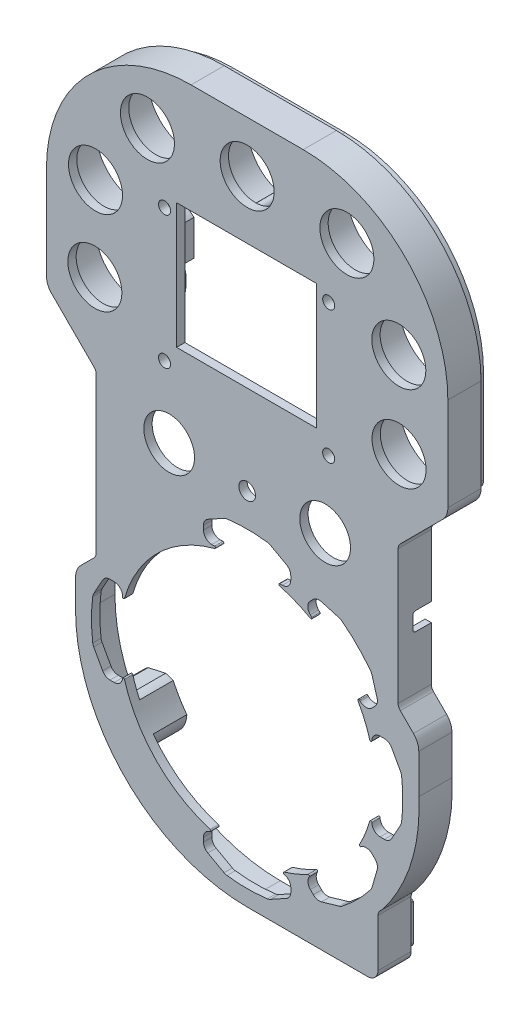
SolidWorks part; units mm, degrees
ref_plane "Front Plane" through (0, 0, 0) normal (0, 0, 1) x (1, 0, 0)
ref_plane "Top Plane" through (0, 0, 0) normal (0, 1, 0) x (1, 0, 0)
ref_plane "Right Plane" through (0, 0, 0) normal (1, 0, 0) x (0, 0, -1)
sketch "Sketch1" plane through (0, 0, 0) normal (0, 0, 1) x (1, 0, 0)
  line L36 (8.4982, -30) -> (7.3207, -30)
  line L37 (-7.3216, -30) -> (-8.502, -30)
  line L38 (-10.502, -32) -> (-10.502, -33.0199)
  line L39 (-9.469, -34.7705) -> (-5.5638, -36.9277)
  line L40 (5.5641, -36.9255) -> (9.4653, -34.7705)
  line L41 (10.4982, -33.0199) -> (10.4982, -32)
  line L42 (27.2278, -15.1986) -> (26.1368, -16.2896)
  line L43 (16.1034, -26.323) -> (15.2069, -27.2195)
  line L44 (15.2069, -30.0479) -> (15.928, -30.7691)
  line L45 (17.8964, -31.2766) -> (22.1831, -30.0405)
  line L46 (30.0502, -22.1703) -> (31.2849, -17.888)
  line L47 (30.7774, -15.9197) -> (30.0563, -15.1986)
  line L48 (29.9995, 8.3209) -> (29.9995, 6.3328)
  line L49 (29.9995, -6.7043) -> (29.9995, -8.6793)
  line L50 (31.9995, -10.6793) -> (33.0194, -10.6793)
  line L51 (34.77, -9.6463) -> (36.9272, -5.7411)
  line L52 (36.925, 5.3868) -> (34.77, 9.2879)
  line L53 (33.0194, 10.3209) -> (31.9995, 10.3209)
  line L54 (15.1817, 27.2112) -> (17.0463, 25.3466)
  line L55 (25.5318, 16.8611) -> (27.2026, 15.1902)
  line L56 (30.0311, 15.1902) -> (30.7522, 15.9114)
  line L57 (31.2597, 17.8797) -> (30.0237, 22.1664)
  line L58 (22.1535, 30.0335) -> (17.8712, 31.2683)
  line L59 (15.9029, 30.7608) -> (15.1817, 30.0396)
  line L60 (-8.5066, 30) -> (-5.5963, 30)
  line L61 (5.5954, 30) -> (8.4935, 30)
  line L62 (10.4935, 32) -> (10.4935, 33.0198)
  line L63 (9.4606, 34.7705) -> (5.5554, 36.9277)
  line L64 (-5.5725, 36.9254) -> (-9.4737, 34.7705)
  line L65 (-10.5066, 33.0198) -> (-10.5066, 32)
  line L66 (-30, -8.5009) -> (-30, -6.7063)
  line L67 (-30, 6.3349) -> (-30, 8.4993)
  line L68 (-32, 10.4993) -> (-33.0198, 10.4993)
  line L69 (-34.7705, 9.4663) -> (-36.9277, 5.5612)
  line L70 (-36.9254, -5.5668) -> (-34.7705, -9.4679)
  line L71 (-33.0198, -10.5009) -> (-32, -10.5009)
  line L101 (-41.299, 6.7982) -> (-41.3, -0.001)
  line L102 (-36.8542, 13.0512) -> (-40.0199, 9.8856)
  line L103 (-36.337, 51.567) -> (-36.337, 14.3015)
  line L104 (-47.0212, 62.9828) -> (-36.8553, 52.8168)
  line L105 (-48.3, 88.5) -> (-48.3, 66.0705)
  line L106 (13.5, 123.3) -> (-13.5, 123.3)
  line L107 (48.309, 66.0795) -> (48.3, 88.5)
  line L108 (36.865, 52.8266) -> (47.0307, 62.9922)
  line L109 (36.337, 19.3) -> (36.337, 51.5682)
  line L110 (40.0202, 14.8852) -> (36.8553, 18.0502)
  line L111 (41.299, 2.3183) -> (41.299, 11.7975)
  line L112 (32.0172, -26.0612) -> (32.5244, -25.5541)
  line L113 (31.5, -38.795) -> (31.5, -27.3095)
  line L114 (0, -41.301) -> (28.9995, -41.301)
  circle A1 centre (-18.768, 46) radius 6.1
  circle A4 centre (18.768, 46) radius 6.1
  arc A45 (17.0463, 25.3466) -> (5.5954, 30) centre (-0.0005, -0.1857) ccw
  arc A77 (-8.502, -30) -> (-10.502, -32) centre (-8.502, -32) ccw
  arc A78 (-10.502, -33.0199) -> (-9.469, -34.7705) centre (-8.502, -33.0199) ccw
  arc A79 (-5.5638, -36.9277) -> (-4.8555, -37.1602) centre (-4.5968, -35.177) ccw
  arc A80 (-4.8555, -37.1602) -> (4.8567, -37.1579) centre (-0.0084, 0) ccw
  arc A81 (4.8567, -37.1579) -> (5.5641, -36.9255) centre (4.5971, -35.1748) ccw
  arc A82 (9.4653, -34.7705) -> (10.4982, -33.0199) centre (8.4982, -33.0199) ccw
  arc A83 (10.4982, -32) -> (8.4982, -30) centre (8.4982, -32) ccw
  arc A88 (15.2069, -27.2195) -> (15.2069, -30.0479) centre (16.6211, -28.6337) ccw
  arc A89 (15.928, -30.7691) -> (17.8964, -31.2766) centre (17.3423, -29.3549) ccw
  arc A90 (22.1831, -30.0405) -> (22.8484, -29.7041) centre (21.629, -28.1188) ccw
  arc A91 (22.8484, -29.7041) -> (29.7143, -22.8348) centre (-0.0004, -0.0005) ccw
  arc A92 (29.7143, -22.8348) -> (30.0502, -22.1703) centre (28.1285, -21.6162) ccw
  arc A93 (31.2849, -17.888) -> (30.7774, -15.9197) centre (29.3632, -17.3339) ccw
  arc A94 (30.0563, -15.1986) -> (27.2278, -15.1986) centre (28.642, -16.6128) ccw
  arc A99 (29.9995, -8.6793) -> (31.9995, -10.6793) centre (31.9995, -8.6793) ccw
  arc A100 (33.0194, -10.6793) -> (34.77, -9.6463) centre (33.0194, -8.6793) ccw
  arc A101 (36.9272, -5.7411) -> (37.1598, -5.0328) centre (35.1766, -4.7741) ccw
  arc A102 (37.1598, -5.0328) -> (37.1574, 4.6794) centre (-0.0005, -0.1857) ccw
  arc A103 (37.1574, 4.6794) -> (36.925, 5.3868) centre (35.1743, 4.4198) ccw
  arc A104 (34.77, 9.2879) -> (33.0194, 10.3209) centre (33.0194, 8.3209) ccw
  arc A105 (31.9995, 10.3209) -> (29.9995, 8.3209) centre (31.9995, 8.3209) ccw
  arc A110 (27.2026, 15.1902) -> (30.0311, 15.1902) centre (28.6169, 16.6045) ccw
  arc A111 (30.7522, 15.9114) -> (31.2597, 17.8797) centre (29.338, 17.3256) ccw
  arc A112 (30.0237, 22.1664) -> (29.6872, 22.8318) centre (28.102, 21.6123) ccw
  arc A113 (29.6872, 22.8318) -> (22.818, 29.6976) centre (-0.0164, -0.0171) ccw
  arc A114 (22.818, 29.6976) -> (22.1535, 30.0335) centre (21.5994, 28.1118) ccw
  arc A115 (17.8712, 31.2683) -> (15.9029, 30.7608) centre (17.3171, 29.3465) ccw
  arc A116 (15.1817, 30.0396) -> (15.1817, 27.2112) centre (16.5959, 28.6254) ccw
  arc A121 (8.4935, 30) -> (10.4935, 32) centre (8.4935, 32) ccw
  arc A122 (10.4935, 33.0198) -> (9.4606, 34.7705) centre (8.4935, 33.0198) ccw
  arc A123 (5.5554, 36.9277) -> (4.8471, 37.1602) centre (4.5884, 35.177) ccw
  arc A124 (4.8471, 37.1602) -> (-4.8651, 37.1579) centre (0, 0) ccw
  arc A125 (-4.8651, 37.1579) -> (-5.5725, 36.9254) centre (-4.6055, 35.1748) ccw
  arc A126 (-9.4737, 34.7705) -> (-10.5066, 33.0198) centre (-8.5066, 33.0198) ccw
  arc A127 (-10.5066, 32) -> (-8.5066, 30) centre (-8.5066, 32) ccw
  arc A132 (-30, 8.4993) -> (-32, 10.4993) centre (-32, 8.4993) ccw
  arc A133 (-33.0198, 10.4993) -> (-34.7705, 9.4663) centre (-33.0198, 8.4993) ccw
  arc A134 (-36.9277, 5.5612) -> (-37.1602, 4.8528) centre (-35.177, 4.5941) ccw
  arc A135 (-37.1602, 4.8528) -> (-37.1579, -4.8594) centre (0, 0.0057) ccw
  arc A136 (-37.1579, -4.8594) -> (-36.9254, -5.5668) centre (-35.1748, -4.5997) ccw
  arc A137 (-34.7705, -9.4679) -> (-33.0198, -10.5009) centre (-33.0198, -8.5009) ccw
  arc A138 (-32, -10.5009) -> (-30, -8.5009) centre (-32, -8.5009) ccw
  circle A139 centre (36.55, 71.3501) radius 6.5
  circle A140 centre (36.5, 92.0001) radius 6.5
  circle A141 centre (23.9999, 109.0001) radius 6.5
  circle A142 centre (0.0001, 111) radius 6.5
  circle A143 centre (-24.0001, 108.9999) radius 6.5
  circle A144 centre (-36.5, 91.9999) radius 6.5
  circle A145 centre (-36.65, 71.6499) radius 6.5
  arc A146 (29.9995, 6.3328) -> (25.5318, 16.8611) centre (-0.0005, -0.1857) ccw
  arc A147 (26.1368, -16.2896) -> (29.9995, -6.7043) centre (-0.0005, -0.1857) ccw
  arc A148 (7.3207, -30) -> (16.1034, -26.323) centre (-0.0005, -0.1857) ccw
  arc A149 (-30, -6.7063) -> (-7.3216, -30) centre (-0.0005, -0.1857) ccw
  arc A157 (-41.3, -0.001) -> (0, -41.301) centre (0.0009, -0.0001) ccw
  arc A158 (-40.0199, 9.8856) -> (-41.299, 6.7982) centre (-36.9358, 6.7992) ccw
  arc A159 (-36.8542, 13.0512) -> (-36.337, 14.3015) centre (-38.1114, 14.3035) ccw
  arc A160 (-5.5963, 30) -> (-30, 6.3349) centre (-0.0005, -0.1857) ccw
  arc A161 (-36.337, 51.567) -> (-36.8553, 52.8168) centre (-38.1114, 51.5635) ccw
  arc A162 (-48.3, 66.0705) -> (-47.0212, 62.9828) centre (-43.9368, 66.0688) ccw
  arc A163 (-13.5, 123.3) -> (-48.3, 88.5) centre (-13.4997, 88.4997) ccw
  arc A164 (48.3, 88.5) -> (13.5, 123.3) centre (13.4997, 88.4997) ccw
  arc A165 (47.0307, 62.9922) -> (48.309, 66.0795) centre (43.9392, 66.0805) ccw
  arc A166 (36.865, 52.8266) -> (36.337, 51.5682) centre (38.1601, 51.5431) ccw
  arc A167 (36.337, 19.3) -> (36.8553, 18.0502) centre (38.1114, 19.3035) ccw
  arc A168 (41.299, 11.7975) -> (40.0202, 14.8852) centre (36.9358, 11.7992) ccw
  arc A169 (32.5244, -25.5541) -> (41.299, 2.3183) centre (0.058, -0.0158) ccw
  arc A170 (32.0172, -26.0612) -> (31.5, -27.3095) centre (33.2632, -27.3088) ccw
  arc A171 (28.9995, -41.301) -> (31.5, -38.795) centre (28.9913, -38.7924) ccw
extrude "Boss-Extrude1" add sketch "Sketch1" along normal blind 2
sketch "Sketch2" plane through (0, 0, 2) normal (0, 0, 1) x (1, 0, 0)
  line L21 (16.773, 59.804) -> (19.873, 59.804)
  line L22 (22.373, 62.304) -> (22.373, 94.804)
  line L23 (19.873, 97.304) -> (16.773, 97.304)
  line L24 (16.773, 97.304) -> (-17.027, 97.304)
  line L28 (-17.027, 59.804) -> (16.773, 59.804)
  line L32 (-22.627, 94.804) -> (-22.627, 62.304)
  line L33 (-20.127, 59.804) -> (-17.027, 59.804)
  line L35 (-17.027, 97.304) -> (-20.127, 97.304)
  line L37 (-17.027, 97.304) -> (16.773, 97.304)
  spline S6 degree 3 poles (19.873, 59.804) (21.3375, 59.804) (22.373, 60.8395) (22.373, 62.304) knots 0 0 0 0 1 1 1 1 weights 1 0.804738 0.804738 1
  spline S7 degree 3 poles (22.373, 94.804) (22.373, 96.2685) (21.3375, 97.304) (19.873, 97.304) knots 0 0 0 0 1 1 1 1 weights 1 0.804738 0.804738 1
  spline S8 degree 3 poles (-20.127, 97.304) (-21.5915, 97.304) (-22.627, 96.2685) (-22.627, 94.804) knots 0 0 0 0 1 1 1 1 weights 1 0.804738 0.804738 1
  spline S9 degree 3 poles (-22.627, 62.304) (-22.627, 60.8395) (-21.5915, 59.804) (-20.127, 59.804) knots 0 0 0 0 1 1 1 1 weights 1 0.804738 0.804738 1
sketch "Sketch3" plane through (0, 0, 2) normal (0, 0, 1) x (1, 0, 0)
  line L64 (-17.027, 99.304) -> (-20.127, 99.304)
  line L65 (-24.627, 94.804) -> (-24.627, 62.304)
  line L66 (-20.127, 57.804) -> (-17.027, 57.804)
  line L67 (-17.027, 57.804) -> (16.773, 57.804)
  line L68 (16.773, 57.804) -> (19.873, 57.804)
  line L69 (24.373, 62.304) -> (24.373, 94.804)
  line L70 (19.873, 99.304) -> (16.773, 99.304)
  line L71 (16.773, 99.304) -> (-17.027, 99.304)
  line L72 (-17.027, 99.304) -> (-20.127, 99.304)
  line L73 (-24.627, 94.804) -> (-24.627, 62.304)
  line L74 (-20.127, 57.804) -> (-17.027, 57.804)
  line L75 (-17.027, 57.804) -> (16.773, 57.804)
  line L76 (16.773, 57.804) -> (19.873, 57.804)
  line L77 (24.373, 62.304) -> (24.373, 94.804)
  line L78 (19.873, 99.304) -> (16.773, 99.304)
  line L79 (16.773, 99.304) -> (-17.027, 99.304)
  arc A29 (-20.127, 99.304) -> (-24.627, 94.804) centre (-20.127, 94.804) ccw
  arc A30 (-24.627, 62.304) -> (-20.127, 57.804) centre (-20.127, 62.304) ccw
  arc A31 (19.873, 57.804) -> (24.373, 62.304) centre (19.873, 62.304) ccw
  arc A32 (24.373, 94.804) -> (19.873, 99.304) centre (19.873, 94.804) ccw
  arc A33 (-20.127, 99.304) -> (-24.627, 94.804) centre (-20.127, 94.804) ccw
  arc A34 (-24.627, 62.304) -> (-20.127, 57.804) centre (-20.127, 62.304) ccw
  arc A35 (19.873, 57.804) -> (24.373, 62.304) centre (19.873, 62.304) ccw
  arc A36 (24.373, 94.804) -> (19.873, 99.304) centre (19.873, 94.804) ccw
  dimension "D1" = 2
sketch "Sketch4" plane through (0, 0, 2) normal (0, 0, 1) x (1, 0, 0)
  line L4 (-16.977, 66.854) -> (16.723, 66.854)
  line L5 (16.723, 66.854) -> (16.723, 97.004)
  line L6 (-16.977, 97.004) -> (-16.977, 66.854)
  line L7 (-16.977, 97.004) -> (16.723, 97.004)
extrude "Cut-Extrude1" cut sketch "Sketch4" against normal through all
sketch "Sketch5" plane through (0, 0, 0) normal (0, 0, 1) x (1, 0, 0)
  line L58 (-22.877, 94.804) -> (-22.877, 62.304)
  line L59 (-20.127, 59.554) -> (-17.027, 59.554)
  line L60 (-17.027, 59.554) -> (16.773, 59.554)
  line L61 (16.773, 59.554) -> (19.873, 59.554)
  line L62 (22.623, 62.304) -> (22.623, 94.804)
  line L63 (19.873, 97.554) -> (16.773, 97.554)
  line L64 (16.773, 97.554) -> (-17.027, 97.554)
  line L65 (-17.027, 97.554) -> (-20.127, 97.554)
  line L66 (-22.877, 94.804) -> (-22.877, 62.304)
  line L67 (-20.127, 59.554) -> (-17.027, 59.554)
  line L68 (-17.027, 59.554) -> (16.773, 59.554)
  line L69 (16.773, 59.554) -> (19.873, 59.554)
  line L70 (22.623, 62.304) -> (22.623, 94.804)
  line L71 (19.873, 97.554) -> (16.773, 97.554)
  line L72 (16.773, 97.554) -> (-17.027, 97.554)
  line L73 (-17.027, 97.554) -> (-20.127, 97.554)
  arc A31 (-22.877, 62.304) -> (-20.127, 59.554) centre (-20.127, 62.304) ccw
  arc A32 (19.873, 59.554) -> (22.623, 62.304) centre (19.873, 62.304) ccw
  arc A33 (22.623, 94.804) -> (19.873, 97.554) centre (19.873, 94.804) ccw
  arc A34 (-20.127, 97.554) -> (-22.877, 94.804) centre (-20.127, 94.804) ccw
  arc A35 (-22.877, 62.304) -> (-20.127, 59.554) centre (-20.127, 62.304) ccw
  arc A36 (19.873, 59.554) -> (22.623, 62.304) centre (19.873, 62.304) ccw
  arc A37 (22.623, 94.804) -> (19.873, 97.554) centre (19.873, 94.804) ccw
  arc A38 (-20.127, 97.554) -> (-22.877, 94.804) centre (-20.127, 94.804) ccw
  dimension "D1" = 0.25
sketch "Sketch8" plane through (0, 0, 2) normal (0, 0, -1) x (-1, 0, 0)
  spline S4 degree 3 poles (21.327, 94.529) (21.327, 97.429) (18.427, 97.429) (18.427, 94.529) (18.427, 91.629) (21.327, 91.629) (21.327, 94.529) (21.327, 97.429) (18.427, 97.429) knots -0.5 0 0 0 0.5 0.5 0.5 1 1 1 1.5 1.5 1.5 weights 1 0.333333 0.333333 1 0.333333 0.333333 1 0.333333 0.333333 only from (21.327, 94.529) to (21.327, 94.529)
  spline S5 degree 3 poles (21.327, 62.579) (21.327, 65.479) (18.427, 65.479) (18.427, 62.579) (18.427, 59.679) (21.327, 59.679) (21.327, 62.579) (21.327, 65.479) (18.427, 65.479) knots -0.5 0 0 0 0.5 0.5 0.5 1 1 1 1.5 1.5 1.5 weights 1 0.333333 0.333333 1 0.333333 0.333333 1 0.333333 0.333333 only from (21.327, 62.579) to (21.327, 62.579)
  spline S6 degree 3 poles (-18.173, 62.579) (-18.173, 65.479) (-21.073, 65.479) (-21.073, 62.579) (-21.073, 59.679) (-18.173, 59.679) (-18.173, 62.579) (-18.173, 65.479) (-21.073, 65.479) knots -0.5 0 0 0 0.5 0.5 0.5 1 1 1 1.5 1.5 1.5 weights 1 0.333333 0.333333 1 0.333333 0.333333 1 0.333333 0.333333 only from (-18.173, 62.579) to (-18.173, 62.579)
  spline S7 degree 3 poles (-18.173, 94.529) (-18.173, 97.429) (-21.073, 97.429) (-21.073, 94.529) (-21.073, 91.629) (-18.173, 91.629) (-18.173, 94.529) (-18.173, 97.429) (-21.073, 97.429) knots -0.5 0 0 0 0.5 0.5 0.5 1 1 1 1.5 1.5 1.5 weights 1 0.333333 0.333333 1 0.333333 0.333333 1 0.333333 0.333333 only from (-18.173, 94.529) to (-18.173, 94.529)
extrude "Cut-Extrude3" cut sketch "Sketch8" along normal through all
sketch "Sketch9" plane through (0, 0, 0) normal (0, 0, -1) x (-1, 0, 0)
  line L100 (-34.837, 51.577) -> (-34.837, 19.2985)
  line L101 (-35.794, 16.9901) -> (-38.9597, 13.8244)
  line L102 (-39.799, 11.7978) -> (-39.799, 2.2755)
  line L103 (-31.4, -24.5571) -> (-30.9569, -25.0002)
  line L104 (-30, -27.3098) -> (-30, -38.7942)
  line L105 (-28.9965, -39.801) -> (0, -39.801)
  line L106 (39.8, -0.0011) -> (39.799, 6.7983)
  line L107 (38.9594, 8.8247) -> (35.7925, 11.9916)
  line L108 (34.837, 14.3006) -> (34.837, 51.5685)
  line L109 (35.794, 53.8769) -> (45.9607, 64.0436)
  line L110 (46.8, 66.0702) -> (46.8, 88.5)
  line L111 (13.5, 121.8) -> (-13.5, 121.8)
  line L112 (-46.8, 88.4997) -> (-46.809, 66.0794)
  line L113 (-45.9698, 64.0526) -> (-35.8023, 53.8852)
  line L114 (41.3, -0.001) -> (41.299, 6.7982)
  line L130 (40.0199, 9.8856) -> (36.8542, 13.0512)
  line L131 (36.337, 14.3015) -> (36.337, 51.567)
  line L132 (36.8553, 52.8168) -> (47.0212, 62.9828)
  line L133 (48.3, 66.0705) -> (48.3, 88.5)
  line L134 (13.5, 123.3) -> (-13.5, 123.3)
  line L135 (-48.3, 88.5) -> (-48.309, 66.0795)
  line L136 (-47.0307, 62.9922) -> (-36.865, 52.8266)
  line L137 (-36.337, 51.5682) -> (-36.337, 19.3)
  line L138 (-36.8553, 18.0502) -> (-40.0202, 14.8852)
  line L139 (-41.299, 11.7975) -> (-41.299, 2.3183)
  line L140 (-32.5244, -25.5541) -> (-32.0172, -26.0612)
  line L141 (-31.5, -27.3095) -> (-31.5, -38.795)
  line L142 (-28.9995, -41.301) -> (0, -41.301)
  line L143 (41.3, -0.001) -> (41.299, 6.7982)
  line L144 (40.0199, 9.8856) -> (36.8542, 13.0512)
  line L145 (36.337, 14.3015) -> (36.337, 51.567)
  line L146 (36.8553, 52.8168) -> (47.0212, 62.9828)
  line L147 (48.3, 66.0705) -> (48.3, 88.5)
  line L148 (13.5, 123.3) -> (-13.5, 123.3)
  line L149 (-48.3, 88.5) -> (-48.309, 66.0795)
  line L150 (-47.0307, 62.9922) -> (-36.865, 52.8266)
  line L151 (-36.337, 51.5682) -> (-36.337, 19.3)
  line L152 (-36.8553, 18.0502) -> (-40.0202, 14.8852)
  line L153 (-41.299, 11.7975) -> (-41.299, 2.3183)
  line L154 (-32.5244, -25.5541) -> (-32.0172, -26.0612)
  line L155 (-31.5, -27.3095) -> (-31.5, -38.795)
  line L156 (-28.9995, -41.301) -> (0, -41.301)
  arc A98 (-35.794, 16.9901) -> (-34.837, 19.2985) centre (-38.1114, 19.3035) ccw
  arc A99 (-38.9597, 13.8244) -> (-39.799, 11.7978) centre (-36.9358, 11.7992) ccw
  arc A100 (-39.799, 2.2755) -> (-31.4, -24.5571) centre (-0.058, -0.0158) ccw
  arc A101 (-30, -27.3098) -> (-30.9569, -25.0002) centre (-33.2632, -27.3088) ccw
  arc A102 (-30, -38.7942) -> (-28.9965, -39.801) centre (-28.9913, -38.7924) ccw
  arc A103 (0, -39.801) -> (39.8, -0.0011) centre (-0.0009, -0.0001) ccw
  arc A104 (39.799, 6.7983) -> (38.9594, 8.8247) centre (36.9358, 6.7992) ccw
  arc A105 (34.837, 14.3006) -> (35.7925, 11.9916) centre (38.1114, 14.3035) ccw
  arc A106 (35.794, 53.8769) -> (34.837, 51.5685) centre (38.1114, 51.5635) ccw
  arc A107 (45.9607, 64.0436) -> (46.8, 66.0702) centre (43.9368, 66.0688) ccw
  arc A108 (46.8, 88.5) -> (13.5, 121.8) centre (13.4997, 88.4997) ccw
  arc A109 (-13.5, 121.8) -> (-46.8, 88.4997) centre (-13.4997, 88.4997) ccw
  arc A110 (-46.809, 66.0794) -> (-45.9698, 64.0526) centre (-43.9392, 66.0805) ccw
  arc A111 (-34.837, 51.577) -> (-35.8023, 53.8852) centre (-38.1601, 51.5431) ccw
  arc A126 (0, -41.301) -> (41.3, -0.001) centre (-0.0009, -0.0001) ccw
  arc A127 (41.299, 6.7982) -> (40.0199, 9.8856) centre (36.9358, 6.7992) ccw
  arc A128 (36.337, 14.3015) -> (36.8542, 13.0512) centre (38.1114, 14.3035) ccw
  arc A129 (36.8553, 52.8168) -> (36.337, 51.567) centre (38.1114, 51.5635) ccw
  arc A130 (47.0212, 62.9828) -> (48.3, 66.0705) centre (43.9368, 66.0688) ccw
  arc A131 (48.3, 88.5) -> (13.5, 123.3) centre (13.4997, 88.4997) ccw
  arc A132 (-13.5, 123.3) -> (-48.3, 88.5) centre (-13.4997, 88.4997) ccw
  arc A133 (-48.309, 66.0795) -> (-47.0307, 62.9922) centre (-43.9392, 66.0805) ccw
  arc A134 (-36.337, 51.5682) -> (-36.865, 52.8266) centre (-38.1601, 51.5431) ccw
  arc A135 (-36.8553, 18.0502) -> (-36.337, 19.3) centre (-38.1114, 19.3035) ccw
  arc A136 (-40.0202, 14.8852) -> (-41.299, 11.7975) centre (-36.9358, 11.7992) ccw
  arc A137 (-41.299, 2.3183) -> (-32.5244, -25.5541) centre (-0.058, -0.0158) ccw
  arc A138 (-31.5, -27.3095) -> (-32.0172, -26.0612) centre (-33.2632, -27.3088) ccw
  arc A139 (-31.5, -38.795) -> (-28.9995, -41.301) centre (-28.9913, -38.7924) ccw
  arc A140 (0, -41.301) -> (41.3, -0.001) centre (-0.0009, -0.0001) ccw
  arc A141 (41.299, 6.7982) -> (40.0199, 9.8856) centre (36.9358, 6.7992) ccw
  arc A142 (36.337, 14.3015) -> (36.8542, 13.0512) centre (38.1114, 14.3035) ccw
  arc A143 (36.8553, 52.8168) -> (36.337, 51.567) centre (38.1114, 51.5635) ccw
  arc A144 (47.0212, 62.9828) -> (48.3, 66.0705) centre (43.9368, 66.0688) ccw
  arc A145 (48.3, 88.5) -> (13.5, 123.3) centre (13.4997, 88.4997) ccw
  arc A146 (-13.5, 123.3) -> (-48.3, 88.5) centre (-13.4997, 88.4997) ccw
  arc A147 (-48.309, 66.0795) -> (-47.0307, 62.9922) centre (-43.9392, 66.0805) ccw
  arc A148 (-36.337, 51.5682) -> (-36.865, 52.8266) centre (-38.1601, 51.5431) ccw
  arc A149 (-36.8553, 18.0502) -> (-36.337, 19.3) centre (-38.1114, 19.3035) ccw
  arc A150 (-40.0202, 14.8852) -> (-41.299, 11.7975) centre (-36.9358, 11.7992) ccw
  arc A151 (-41.299, 2.3183) -> (-32.5244, -25.5541) centre (-0.058, -0.0158) ccw
  arc A152 (-31.5, -27.3095) -> (-32.0172, -26.0612) centre (-33.2632, -27.3088) ccw
  arc A153 (-31.5, -38.795) -> (-28.9995, -41.301) centre (-28.9913, -38.7924) ccw
  dimension "D1" = 0
  dimension "D2" = 1.5
extrude "Boss-Extrude4" add sketch "Sketch9" along normal offset from surface (5.98 mm away) 0.25
sketch "Sketch10" plane through (0, 0, 0) normal (-1, 0, 0) x (0, 0, 1)
  line L11 (-5.23, 36.55) -> (-2.23, 36.55)
  line L14 (-5.23, 32.15) -> (-2.23, 32.15)
  line L18 (-5.23, 36.55) -> (-5.98, 36.55)
  line L20 (-1.53, 32.85) -> (-1.53, 35.85)
  line L22 (-5.98, 36.55) -> (-5.98, 32.15)
  line L23 (-5.98, 32.15) -> (-5.23, 32.15)
  arc A20 (-1.735, 36.345) -> (-2.23, 36.55) centre (-2.23, 35.85) ccw
  arc A21 (-1.53, 35.85) -> (-1.735, 36.345) centre (-2.23, 35.85) ccw
  arc A22 (-2.23, 32.15) -> (-1.735, 32.355) centre (-2.23, 32.85) ccw
  arc A23 (-1.735, 32.355) -> (-1.53, 32.85) centre (-2.23, 32.85) ccw
extrude "Cut-Extrude4" cut sketch "Sketch10" against normal through all and the other way through all
sketch "Sketch11" plane through (0, 0, 0) normal (0, 0, -1) x (-1, 0, 0)
  line L1 (-1.3223, 99.1737) -> (1.3221, 99.1737)
  line L4 (1.0999, 102.8) -> (1.0999, 101.1613)
  line L5 (-1.1001, 101.1613) -> (-1.1001, 102.8)
  line L6 (1.0999, 102.8) -> (1.0999, 101.1613)
  line L7 (-1.1001, 101.1613) -> (-1.1001, 102.8)
  line L9 (39.5906, 60.1189) -> (42.7783, 60.9319)
  line L10 (-25.0999, 117.2001) -> (-25.0999, 118.8388)
  line L11 (-22.8999, 118.8388) -> (-22.8999, 117.2001)
  line L12 (-25.0999, 117.2001) -> (-25.0999, 118.8388)
  line L13 (-22.8999, 118.8388) -> (-22.8999, 117.2001)
  line L16 (-37.6, 100.2001) -> (-37.6, 101.8388)
  line L17 (-35.4, 101.8388) -> (-35.4, 100.2001)
  line L18 (-37.6, 100.2001) -> (-37.6, 101.8388)
  line L19 (-35.4, 101.8388) -> (-35.4, 100.2001)
  line L22 (-37.65, 79.5501) -> (-37.65, 81.1888)
  line L23 (-35.45, 81.1888) -> (-35.45, 79.5501)
  line L24 (-37.65, 79.5501) -> (-37.65, 81.1888)
  line L25 (-35.45, 81.1888) -> (-35.45, 79.5501)
  line L26 (11.2056, 106.9947) -> (12.2702, 106.9947)
  line L27 (-12.2701, 106.9947) -> (-11.2058, 106.9947)
  line L28 (22.9001, 117.1999) -> (22.9001, 118.8386)
  line L29 (25.1001, 118.8386) -> (25.1001, 117.1999)
  line L30 (22.9001, 117.1999) -> (22.9001, 118.8386)
  line L31 (25.1001, 118.8386) -> (25.1001, 117.1999)
  line L32 (-45.9698, 64.0526) -> (-35.8023, 53.8852) construction
  line L33 (-46.8, 88.4997) -> (-46.809, 66.0794) construction
  line L34 (35.4, 100.1999) -> (35.4, 101.8386)
  line L35 (37.6, 101.8386) -> (37.6, 100.1999)
  line L36 (35.4, 100.1999) -> (35.4, 101.8386)
  line L37 (37.6, 101.8386) -> (37.6, 100.1999)
  line L38 (35.794, 53.8769) -> (45.9607, 64.0436) construction
  line L39 (46.8, 66.0702) -> (46.8, 88.5) construction
  line L40 (35.55, 79.8499) -> (35.55, 81.4886)
  line L41 (37.75, 81.4886) -> (37.75, 79.8499)
  line L42 (35.55, 79.8499) -> (35.55, 81.4886)
  line L43 (37.75, 81.4886) -> (37.75, 79.8499)
  line L44 (13.5, 121.8) -> (-13.5, 121.8) construction
  line L45 (-45.9698, 64.0526) -> (-44.1221, 62.205)
  line L46 (-46.8, 88.4997) -> (-46.809, 66.0794)
  line L47 (42.9233, 61.0061) -> (45.9607, 64.0436)
  line L48 (46.8, 66.0702) -> (46.8, 88.5)
  line L49 (13.5, 121.8) -> (-13.5, 121.8)
  arc A0 (-11.2058, 106.9947) -> (-1.3223, 99.1737) centre (-0.0001, 111) ccw
  arc A3 (-25.8154, 97.2393) -> (-12.2701, 106.9947) centre (-23.9999, 109) ccw
  arc A4 (1.0999, 101.1613) -> (-1.1001, 101.1613) centre (-0.0001, 111) ccw
  arc A5 (1.0999, 102.8) -> (-1.1001, 102.8) centre (-0.0001, 102.8) ccw
  arc A6 (1.0999, 101.1613) -> (-1.1001, 101.1613) centre (-0.0001, 111) ccw
  arc A7 (1.0999, 102.8) -> (-1.1001, 102.8) centre (-0.0001, 102.8) ccw
  arc A10 (-25.0999, 118.8388) -> (-22.8999, 118.8388) centre (-23.9999, 109.0001) ccw
  arc A11 (-25.0999, 117.2001) -> (-22.8999, 117.2001) centre (-23.9999, 117.2001) ccw
  arc A13 (-25.0999, 117.2001) -> (-22.8999, 117.2001) centre (-23.9999, 117.2001) ccw
  arc A14 (-30.6086, 81.6607) -> (-25.8154, 97.2393) centre (-36.5, 92.0001) ccw
  arc A16 (-37.6, 101.8388) -> (-35.4, 101.8388) centre (-36.5, 92.0001) ccw
  arc A17 (-37.6, 100.2001) -> (-35.4, 100.2001) centre (-36.5, 100.2001) ccw
  arc A18 (-37.6, 101.8388) -> (-35.4, 101.8388) centre (-36.5, 92.0001) ccw
  arc A19 (-37.6, 100.2001) -> (-35.4, 100.2001) centre (-36.5, 100.2001) ccw
  arc A20 (-43.6373, 61.7909) -> (-30.6086, 81.6607) centre (-36.5496, 71.3498) ccw
  arc A22 (-37.65, 81.1888) -> (-35.45, 81.1888) centre (-36.55, 71.3501) ccw
  arc A23 (-37.65, 79.5501) -> (-35.45, 79.5501) centre (-36.55, 79.5501) ccw
  arc A24 (-37.65, 81.1888) -> (-35.45, 81.1888) centre (-36.55, 71.3501) ccw
  arc A25 (-37.65, 79.5501) -> (-35.45, 79.5501) centre (-36.55, 79.5501) ccw
  arc A26 (25.8154, 97.2392) -> (30.4047, 81.7794) centre (36.5, 91.9999) ccw
  arc A28 (22.9001, 118.8386) -> (25.1001, 118.8386) centre (24.0001, 108.9999) ccw
  arc A29 (22.9001, 117.1999) -> (25.1001, 117.1999) centre (24.0001, 117.1999) ccw
  arc A30 (22.9001, 118.8386) -> (25.1001, 118.8386) centre (24.0001, 108.9999) ccw
  arc A31 (22.9001, 117.1999) -> (25.1001, 117.1999) centre (24.0001, 117.1999) ccw
  arc A32 (-25.0999, 118.8387) -> (-22.8999, 118.8387) centre (-23.9999, 109) ccw
  arc A34 (35.4, 101.8386) -> (37.6, 101.8386) centre (36.5, 91.9999) ccw
  arc A35 (35.4, 100.1999) -> (37.6, 100.1999) centre (36.5, 100.1999) ccw
  arc A36 (35.4, 101.8386) -> (37.6, 101.8386) centre (36.5, 91.9999) ccw
  arc A37 (35.4, 100.1999) -> (37.6, 100.1999) centre (36.5, 100.1999) ccw
  arc A38 (1.3221, 99.1737) -> (11.2056, 106.9947) centre (-0.0001, 111) ccw
  arc A40 (35.55, 81.4886) -> (37.75, 81.4886) centre (36.65, 71.6499) ccw
  arc A41 (35.55, 79.8499) -> (37.75, 79.8499) centre (36.65, 79.8499) ccw
  arc A42 (35.55, 81.4886) -> (37.75, 81.4886) centre (36.65, 71.6499) ccw
  arc A43 (35.55, 79.8499) -> (37.75, 79.8499) centre (36.65, 79.8499) ccw
  arc A44 (12.2702, 106.9947) -> (25.8154, 97.2392) centre (24.0001, 108.9999) ccw
  arc A48 (30.4047, 81.7794) -> (39.5906, 60.1189) centre (36.65, 71.6499) ccw
  arc A49 (-46.809, 66.0794) -> (-45.9698, 64.0526) centre (-43.9392, 66.0805) ccw construction
  arc A50 (45.9607, 64.0436) -> (46.8, 66.0702) centre (43.9368, 66.0688) ccw construction
  arc A51 (46.8, 88.5) -> (13.5, 121.8) centre (13.4997, 88.4997) ccw construction
  arc A52 (-13.5, 121.8) -> (-46.8, 88.4997) centre (-13.4997, 88.4997) ccw construction
  arc A53 (-46.809, 66.0794) -> (-45.9698, 64.0526) centre (-43.9392, 66.0805) ccw
  arc A54 (45.9607, 64.0436) -> (46.8, 66.0702) centre (43.9368, 66.0688) ccw
  arc A55 (46.8, 88.5) -> (13.5, 121.8) centre (13.4997, 88.4997) ccw
  arc A56 (-13.5, 121.8) -> (-46.8, 88.4997) centre (-13.4997, 88.4997) ccw
  arc A57 (-43.6373, 61.7909) -> (-44.185, 62.2678) centre (-40.8788, 65.5111) cw
  arc A58 (42.7783, 60.9319) -> (42.9233, 61.0061) centre (42.6876, 61.2876) ccw
  point P4 (-25.3221, 120.8264)
  point P5 (-22.6777, 120.8264)
  point P7 (22.6778, 120.8262)
  point P8 (25.3223, 120.8262)
  point P48 (35.1777, 103.8262)
  point P49 (37.8222, 103.8262)
  point P55 (-37.8222, 103.8264)
  point P56 (-35.1777, 103.8264)
  point P58 (-37.8722, 83.1764)
  point P59 (-35.2277, 83.1764)
  point P61 (35.3277, 83.4762)
  point P62 (37.9722, 83.4762)
  dimension "D1" = 0.4
  dimension "D2" = 0.4
  dimension "D3" = 0.4
  dimension "D4" = 0.4
  dimension "D5" = 0.4
  dimension "D6" = 0.4
  dimension "D7" = 0.4
extrude "Boss-Extrude5" add sketch "Sketch11" along normal up to surface (8.08 mm away) contours L9 A58 L47 A54 L48 A55 L49 A56 L46 A53 L45 A57 A20 A14 A3 L27 A0 L1 A38 L26 A44 A26 A48 L42 A43 L43 A42 L36 A37 L37 A36 L30 A31 L31 A30 L24 A25 L25 A24 L18 A19 L19 A18 L6
sketch "Sketch12" plane through (0, 0, -8.08) normal (0, 0, -1) x (-1, 0, 0)
  line L21 (31.8245, 61.8175) -> (28.7175, 64.9245)
  line L22 (31.8245, 61.8175) -> (28.7175, 64.9245)
  line L24 (24.9755, 61.1825) -> (28.0825, 58.0755)
  line L25 (24.9755, 61.1825) -> (28.0825, 58.0755)
  line L31 (24.3914, 63.3533) -> (24.7506, 63.7125)
  line L32 (24.3914, 63.3533) -> (24.7506, 63.7125)
  line L33 (24.9755, 61.1825) -> (24.3914, 63.3533)
  line L34 (30.6125, 57.8506) -> (30.2533, 57.4914)
  line L35 (30.6125, 57.8506) -> (30.2533, 57.4914)
  line L38 (26.5466, 65.5086) -> (26.1874, 65.1494)
  line L39 (26.5466, 65.5086) -> (26.1874, 65.1494)
  line L40 (24.7506, 63.7125) -> (26.1874, 65.1494)
  line L41 (32.4086, 59.6467) -> (32.0494, 59.2875)
  line L42 (32.4086, 59.6467) -> (32.0494, 59.2875)
  line L43 (26.5466, 65.5086) -> (28.7175, 64.9245)
  line L44 (31.8245, 61.8175) -> (32.4086, 59.6467)
  line L45 (32.0494, 59.2875) -> (30.6125, 57.8506)
  line L46 (30.6125, 57.8506) -> (30.2533, 57.4914)
  line L47 (28.0825, 58.0755) -> (30.2533, 57.4914)
  dimension "D5" = 0.5
  dimension "D1" = 0.5
  dimension "D2" = 0.5
  dimension "D3" = 0.5
  dimension "D4" = 0.5
  dimension "D6" = 0.5
extrude "Cut-Extrude5" cut sketch "Sketch12" against normal blind 3
sketch "Sketch13" plane through (-36.337, 0, 0) normal (-1, 0, 0) x (0, 0, 1)
  arc A4 (-6.37, 50.3249) -> (-6.37, 47.7249) centre (-6.37, 49.0249) ccw
  arc A5 (-6.37, 47.7249) -> (-6.37, 50.3249) centre (-6.37, 49.0249) ccw
  arc A6 (-6.37, 50.3249) -> (-6.37, 47.7249) centre (-6.37, 49.0249) ccw
  arc A7 (-6.37, 47.7249) -> (-6.37, 50.3249) centre (-6.37, 49.0249) ccw
  arc A12 (-6.37, 43.6999) -> (-6.37, 41.0999) centre (-6.37, 42.3999) ccw
  arc A13 (-6.37, 41.0999) -> (-6.37, 43.6999) centre (-6.37, 42.3999) ccw
  arc A14 (-6.37, 43.6999) -> (-6.37, 41.0999) centre (-6.37, 42.3999) ccw
  arc A15 (-6.37, 41.0999) -> (-6.37, 43.6999) centre (-6.37, 42.3999) ccw
  dimension "D1" = 0.4
  dimension "D2" = 0.4
extrude "Cut-Extrude6" cut sketch "Sketch13" against normal blind 10
sketch "Sketch14" plane through (0, 0, 0) normal (0, 0, -1) x (-1, 0, 0)
  circle A0 centre (-31.7, 57.8) radius 1.5 construction
  circle A1 centre (-26.7, -35.2) radius 1.5 construction
  circle A2 centre (30.6, -18.4) radius 1.5 construction
  circle A3 centre (29.7, 22.6) radius 1.5 construction
  circle A4 centre (27.1, 81.7) radius 1.5 construction
  circle A5 centre (10.7, 101.6) radius 1.5 construction
  circle A6 centre (-37.6, 105.6) radius 1.5 construction
  circle A7 centre (-31.7, 57.8) radius 1.5
  circle A8 centre (-26.7, -35.2) radius 1.5
  circle A9 centre (30.6, -18.4) radius 1.5
  circle A10 centre (29.7, 22.6) radius 1.5
  circle A11 centre (27.1, 81.7) radius 1.5
  circle A12 centre (10.7, 101.6) radius 1.5
  circle A13 centre (-37.6, 105.6) radius 1.5
sketch "Sketch15" plane through (0, 0, 0) normal (0, 0, -1) x (-1, 0, 0)
  line L3 (6.2694, 97.554) -> (15.1306, 97.554)
  line L5 (22.877, 85.9622) -> (22.877, 77.4378)
  line L9 (34.787, 19.4184) -> (34.787, 25.7816)
  line L12 (-28.9964, -39.751) -> (-23.0466, -39.751)
  line L13 (-29.95, -30.1564) -> (-29.95, -38.7943)
  line L14 (-27.6208, -29.2711) -> (-23.0466, -32.6383)
  line L15 (-23.0466, -32.6383) -> (-23.0466, -39.751)
  line L16 (29.7, -12.4679) -> (33.9142, -13.3984)
  line L17 (-27.6208, 53.4) -> (-27.6208, 58.2791)
  line L18 (-27.6208, 58.2791) -> (-25.7192, 58.2791)
  line L25 (11.2056, 106.9947) -> (12.2702, 106.9947) construction
  line L27 (11.2056, 106.9947) -> (12.2702, 106.9947)
  line L30 (-43.6373, 61.7909) -> (-35.7669, 53.9205)
  circle A0 centre (-37.6, 105.6) radius 1.25
  circle A1 centre (10.7, 101.6) radius 1.25
  circle A2 centre (27.1, 81.7) radius 1.25
  circle A3 centre (-31.7, 57.8) radius 1.25
  circle A4 centre (29.7, 22.6) radius 1.25
  circle A5 centre (30.6, -18.4) radius 1.25
  circle A6 centre (-26.7, -35.2) radius 1.25
  arc A15 (4.8788, 100.1462) -> (6.2694, 97.554) centre (10.7, 101.6) ccw
  arc A21 (15.1306, 97.554) -> (16.4295, 99.8186) centre (10.7, 101.6) ccw
  arc A22 (22.877, 77.4378) -> (25.5375, 75.907) centre (27.1, 81.7) ccw
  arc A25 (30.4047, 81.7794) -> (25.5375, 75.907) centre (36.65, 71.6499) ccw
  arc A26 (25.4916, 87.4804) -> (30.4047, 81.7794) centre (36.5, 91.9999) ccw
  arc A27 (25.4916, 87.4804) -> (22.877, 85.9622) centre (27.1, 81.7) ccw
  arc A33 (-35.0345, 52.8119) -> (-27.6208, 53.4) centre (-31.7, 57.8) ccw
  arc A34 (34.787, 25.7816) -> (34.787, 19.4184) centre (29.7, 22.6) ccw
  arc A35 (36.2358, -16.3414) -> (33.9142, -13.3984) centre (30.6, -18.4) ccw
  arc A39 (24.6019, -18.5503) -> (27.8725, -13.0558) centre (0.0005, -0.1857) ccw
  arc A40 (24.6019, -18.5503) -> (31.4244, -24.3431) centre (30.6, -18.4) ccw
  arc A42 (31.4244, -24.3431) -> (36.2358, -16.3414) centre (-0.0009, -0.0001) ccw
  arc A43 (-27.6208, -29.2711) -> (-29.95, -30.1564) centre (-26.7, -35.2) ccw
  arc A45 (-29.95, -38.7943) -> (-28.9964, -39.751) centre (-28.9913, -38.7924) ccw
  arc A46 (29.7, -12.4679) -> (27.8725, -13.0558) centre (30.6, -18.4) ccw
  arc A47 (-25.7192, 58.2791) -> (-28.3185, 62.7563) centre (-31.7, 57.8) ccw
  arc A55 (4.8788, 100.1462) -> (11.2056, 106.9947) centre (-0.0001, 111) ccw
  arc A56 (12.2702, 106.9947) -> (16.4295, 99.8186) centre (24.0001, 108.9999) ccw
  arc A74 (-43.6373, 61.7909) -> (-28.3185, 62.7563) centre (-36.55, 71.3501) ccw
  arc A75 (-35.0345, 52.8119) -> (-35.7669, 53.9205) centre (-38.1602, 51.5431) ccw
extrude "Boss-Extrude6" add sketch "Sketch15" along normal up to surface (8.08 mm away) contours A75 A33 L17 L18 A47 A74 L30 A3 | A56 L27 A55 A15 L3 A21 A1 | A26 A27 L5 A22 A25 A2 | L9 A34 A4 | L16 A46 A39 A40 A42 A35 A5 | L13 A45 L12 L15 L14 A43 A6 up to face at (-6.7932, 81.6492, -8.08)
sketch "Sketch19" plane through (0, 0, -8.08) normal (0, 0, -1) x (-1, 0, 0)
  circle A1 centre (-37.6, 105.6) radius 1.25
extrude "Cut-Extrude10" cut sketch "Sketch19" against normal up to surface (8.08 mm away) up to face at (27.1423, -35.0727, 0)
fillet "Fillet1" radius 0.25 12 edges at (-30, 6.3349, 1) (-30, -6.7063, 1) (-7.3216, -30, 1) (7.3207, -30, 1) (16.1034, -26.323, 1) (29.9995, -6.7043, 1) (26.1368, -16.2896, 1) (29.9995, 6.3328, 1) (25.5318, 16.8611, 1) (17.0463, 25.3466, 1) (5.5954, 30, 1) (-5.5963, 30, 1)
sketch "Sketch16" plane through (0, -41.301, 0) normal (0, -1, 0) x (1, 0, 0)
  line L0 (13.63, -6.02) -> (13.63, -6.68) construction
  line L1 (14.88, -7.93) -> (17.8118, -7.93) construction
  line L2 (17.8318, -7.93) -> (21.32, -7.93) construction
  line L3 (22.57, -6.68) -> (22.57, -6.02) construction
  line L4 (21.32, -4.77) -> (14.88, -4.77) construction
  line L5 (13.63, -6.02) -> (13.63, -6.68)
  line L6 (14.88, -7.93) -> (17.8118, -7.93)
  line L7 (17.8318, -7.93) -> (21.32, -7.93)
  line L8 (22.57, -6.68) -> (22.57, -6.02)
  line L9 (21.32, -4.77) -> (14.88, -4.77)
  spline S0 degree 3 poles (13.63, -6.02) (13.63, -5.2878) (14.1478, -4.77) (14.88, -4.77) knots 0 0 0 0 1 1 1 1 weights 1 0.804738 0.804738 1 construction
  spline S1 degree 3 poles (14.88, -7.93) (14.1478, -7.93) (13.63, -7.4122) (13.63, -6.68) knots 0 0 0 0 1 1 1 1 weights 1 0.804738 0.804738 1 construction
  spline S2 degree 3 poles (22.57, -6.68) (22.57, -7.4122) (22.0523, -7.93) (21.32, -7.93) knots 0 0 0 0 1 1 1 1 weights 1 0.804738 0.804738 1 construction
  spline S3 degree 3 poles (21.32, -4.77) (22.0523, -4.77) (22.57, -5.2878) (22.57, -6.02) knots 0 0 0 0 1 1 1 1 weights 1 0.804738 0.804738 1 construction
  spline S4 degree 3 poles (13.63, -6.02) (13.63, -5.2878) (14.1478, -4.77) (14.88, -4.77) knots 0 0 0 0 1 1 1 1 weights 1 0.804738 0.804738 1
  spline S5 degree 3 poles (14.88, -7.93) (14.1478, -7.93) (13.63, -7.4122) (13.63, -6.68) knots 0 0 0 0 1 1 1 1 weights 1 0.804738 0.804738 1
  spline S6 degree 3 poles (22.57, -6.68) (22.57, -7.4122) (22.0523, -7.93) (21.32, -7.93) knots 0 0 0 0 1 1 1 1 weights 1 0.804738 0.804738 1
  spline S7 degree 3 poles (21.32, -4.77) (22.0523, -4.77) (22.57, -5.2878) (22.57, -6.02) knots 0 0 0 0 1 1 1 1 weights 1 0.804738 0.804738 1
sketch "Sketch17" plane through (0, 0, -5.98) normal (0, 0, -1) x (-1, 0, 0)
  line L0 (-28.999, -41.001) -> (0, -41.001) construction
  line L1 (41, -0.001) -> (40.999, 6.7981) construction
  line L2 (39.8078, 9.6734) -> (36.6421, 12.8391) construction
  line L3 (36.037, 14.3011) -> (36.037, 32.15) construction
  line L4 (36.037, 36.55) -> (36.037, 41.1598) construction
  line L5 (36.037, 43.64) -> (36.037, 47.7848) construction
  line L6 (36.037, 50.265) -> (36.037, 51.567) construction
  line L7 (36.6429, 53.0287) -> (46.8091, 63.1949) construction
  line L8 (48, 66.0704) -> (48, 88.5) construction
  line L9 (13.5, 123) -> (-13.5, 123) construction
  line L10 (-28.999, -41.001) -> (0, -41.001)
  line L11 (41, -0.001) -> (40.999, 6.7981)
  line L12 (39.8078, 9.6734) -> (36.6421, 12.8391)
  line L13 (36.037, 14.3011) -> (36.037, 32.15)
  line L14 (36.037, 36.55) -> (36.037, 41.1598)
  line L15 (36.037, 43.64) -> (36.037, 47.7848)
  line L16 (36.037, 50.265) -> (36.037, 51.567)
  line L17 (36.6429, 53.0287) -> (46.8091, 63.1949)
  line L18 (48, 66.0704) -> (48, 88.5)
  line L19 (13.5, 123) -> (-13.5, 123)
  line L20 (-28.999, -41.001) -> (0, -41.001) construction
  line L21 (-28.999, -41.001) -> (0, -41.001)
  line L22 (-48, 88.5) -> (-48.009, 66.0794) construction
  line L23 (-46.8185, 63.2043) -> (-36.6524, 53.0382) construction
  line L24 (-36.037, 51.5702) -> (-36.037, 36.55) construction
  line L25 (-36.037, 32.15) -> (-36.037, 19.3) construction
  line L26 (-36.6429, 17.8383) -> (-39.8081, 14.6731) construction
  line L27 (-40.999, 11.7976) -> (-40.999, 2.3098) construction
  line L28 (-32.2996, -25.3546) -> (-31.8051, -25.8491) construction
  line L29 (-31.2, -27.3096) -> (-31.2, -38.795) construction
  line L30 (-48, 88.5) -> (-48.009, 66.0794)
  line L31 (-46.8185, 63.2043) -> (-36.6524, 53.0382)
  line L32 (-36.037, 51.5702) -> (-36.037, 36.55)
  line L33 (-36.037, 32.15) -> (-36.037, 19.3)
  line L34 (-36.6429, 17.8383) -> (-39.8081, 14.6731)
  line L35 (-40.999, 11.7976) -> (-40.999, 2.3098)
  line L36 (-32.2996, -25.3546) -> (-31.8051, -25.8491)
  line L37 (-31.2, -27.3096) -> (-31.2, -38.795)
  line L38 (35.637, 36.55) -> (35.637, 41.1598)
  line L39 (35.637, 43.64) -> (35.637, 47.7848)
  line L40 (35.637, 50.265) -> (35.637, 51.5673)
  line L41 (36.3599, 53.3114) -> (46.5263, 63.4778)
  line L42 (47.6, 66.0703) -> (47.6, 88.5)
  line L43 (13.5, 122.6) -> (-13.5, 122.6)
  line L44 (-47.6, 88.4999) -> (-47.609, 66.0794)
  line L45 (-46.5356, 63.487) -> (-36.369, 53.3205)
  line L46 (-35.637, 51.5727) -> (-35.637, 36.55)
  line L47 (-35.637, 32.15) -> (-35.637, 19.2997)
  line L48 (-36.3599, 17.5556) -> (-39.5253, 14.3902)
  line L49 (-40.599, 11.7977) -> (-40.599, 2.2984)
  line L50 (-31.9998, -25.0887) -> (-31.5223, -25.5662)
  line L51 (-30.8, -27.3097) -> (-30.8, -38.7948)
  line L52 (-28.9983, -40.601) -> (0, -40.601)
  line L53 (-28.999, -40.601) -> (0, -40.601)
  line L54 (40.6, -0.001) -> (40.599, 6.7982)
  line L55 (39.5251, 9.3905) -> (36.359, 12.5565)
  line L56 (35.637, 14.3009) -> (35.637, 32.15)
  line L57 (0, -40.601) -> (0, -41.001)
  line L58 (-28.999, -40.601) -> (-28.999, -41.001)
  line L59 (35.637, 32.15) -> (36.037, 32.15)
  line L60 (35.637, 36.55) -> (36.037, 36.55)
  line L61 (35.637, 41.1598) -> (36.037, 41.1598)
  line L62 (35.637, 47.7848) -> (36.037, 47.7848)
  line L63 (35.637, 50.265) -> (36.037, 50.265)
  line L64 (35.637, 43.64) -> (36.037, 43.64)
  line L65 (-36.037, 32.15) -> (-35.637, 32.15)
  line L66 (-36.037, 36.55) -> (-35.637, 36.55)
  arc A0 (0, -41.001) -> (41, -0.001) centre (-0.0009, -0.0001) ccw construction
  arc A1 (40.999, 6.7981) -> (39.8078, 9.6734) centre (36.9358, 6.7992) ccw construction
  arc A2 (36.037, 14.3011) -> (36.6421, 12.8391) centre (38.1114, 14.3035) ccw construction
  arc A3 (36.6429, 53.0287) -> (36.037, 51.567) centre (38.1114, 51.5635) ccw construction
  arc A4 (46.8091, 63.1949) -> (48, 66.0704) centre (43.9368, 66.0688) ccw construction
  arc A5 (48, 88.5) -> (13.5, 123) centre (13.4997, 88.4997) ccw construction
  arc A6 (0, -41.001) -> (41, -0.001) centre (-0.0009, -0.0001) ccw
  arc A7 (40.999, 6.7981) -> (39.8078, 9.6734) centre (36.9358, 6.7992) ccw
  arc A8 (36.037, 14.3011) -> (36.6421, 12.8391) centre (38.1114, 14.3035) ccw
  arc A9 (36.6429, 53.0287) -> (36.037, 51.567) centre (38.1114, 51.5635) ccw
  arc A10 (46.8091, 63.1949) -> (48, 66.0704) centre (43.9368, 66.0688) ccw
  arc A11 (48, 88.5) -> (13.5, 123) centre (13.4997, 88.4997) ccw
  arc A12 (-13.5, 123) -> (-48, 88.5) centre (-13.4997, 88.4997) ccw construction
  arc A13 (-48.009, 66.0794) -> (-46.8185, 63.2043) centre (-43.9392, 66.0805) ccw construction
  arc A14 (-36.037, 51.5702) -> (-36.6524, 53.0382) centre (-38.1602, 51.5431) ccw construction
  arc A15 (-36.6429, 17.8383) -> (-36.037, 19.3) centre (-38.1114, 19.3035) ccw construction
  arc A16 (-39.8081, 14.6731) -> (-40.999, 11.7976) centre (-36.9358, 11.7992) ccw construction
  arc A17 (-40.999, 2.3098) -> (-32.2996, -25.3546) centre (-0.058, -0.0158) ccw construction
  arc A18 (-31.2, -27.3096) -> (-31.8051, -25.8491) centre (-33.2632, -27.3088) ccw construction
  arc A19 (-31.2, -38.795) -> (-28.999, -41.001) centre (-28.9913, -38.7924) ccw construction
  arc A20 (-13.5, 123) -> (-48, 88.5) centre (-13.4997, 88.4997) ccw
  arc A21 (-48.009, 66.0794) -> (-46.8185, 63.2043) centre (-43.9392, 66.0805) ccw
  arc A22 (-36.037, 51.5702) -> (-36.6524, 53.0382) centre (-38.1602, 51.5431) ccw
  arc A23 (-36.6429, 17.8383) -> (-36.037, 19.3) centre (-38.1114, 19.3035) ccw
  arc A24 (-39.8081, 14.6731) -> (-40.999, 11.7976) centre (-36.9358, 11.7992) ccw
  arc A25 (-40.999, 2.3098) -> (-32.2996, -25.3546) centre (-0.058, -0.0158) ccw
  arc A26 (-31.2, -27.3096) -> (-31.8051, -25.8491) centre (-33.2632, -27.3088) ccw
  arc A27 (-31.2, -38.795) -> (-28.999, -41.001) centre (-28.9913, -38.7924) ccw
  arc A28 (36.3599, 53.3114) -> (35.637, 51.5673) centre (38.1114, 51.5635) ccw
  arc A29 (46.5263, 63.4778) -> (47.6, 66.0703) centre (43.9368, 66.0688) ccw
  arc A30 (47.6, 88.5) -> (13.5, 122.6) centre (13.4997, 88.4997) ccw
  arc A31 (-13.5, 122.6) -> (-47.6, 88.4999) centre (-13.4997, 88.4997) ccw
  arc A32 (-47.609, 66.0794) -> (-46.5356, 63.487) centre (-43.9392, 66.0805) ccw
  arc A33 (-35.637, 51.5727) -> (-36.369, 53.3205) centre (-38.1602, 51.5431) ccw
  arc A34 (-36.3599, 17.5556) -> (-35.637, 19.2997) centre (-38.1114, 19.3035) ccw
  arc A35 (-39.5253, 14.3902) -> (-40.599, 11.7977) centre (-36.9358, 11.7992) ccw
  arc A36 (-40.599, 2.2984) -> (-31.9998, -25.0887) centre (-0.058, -0.0158) ccw
  arc A37 (-30.8, -27.3097) -> (-31.5223, -25.5662) centre (-33.2632, -27.3088) ccw
  arc A38 (-30.8, -38.7948) -> (-28.9983, -40.601) centre (-28.9913, -38.7924) ccw
  arc A39 (0, -40.601) -> (40.6, -0.001) centre (-0.0009, -0.0001) ccw
  arc A40 (40.599, 6.7982) -> (39.5251, 9.3905) centre (36.9358, 6.7992) ccw
  arc A41 (35.637, 14.3009) -> (36.359, 12.5565) centre (38.1114, 14.3035) ccw
  dimension "D1" = 0.4
  dimension "D2" = 0.4
  dimension "D3" = 0.4
sketch "Sketch18" plane through (0, 0, 2) normal (0, 0, 1) x (1, 0, 0)
  spline S0 degree 3 poles (-0.0001, 47.4) (-4.0001, 47.4) (-4.0001, 43.4) (-0.0001, 43.4) (3.9999, 43.4) (3.9999, 47.4) (-0.0001, 47.4) (-4.0001, 47.4) (-4.0001, 43.4) knots -0.5 0 0 0 0.5 0.5 0.5 1 1 1 1.5 1.5 1.5 weights 1 0.333333 0.333333 1 0.333333 0.333333 1 0.333333 0.333333 only from (-0.0001, 47.4) to (-0.0001, 47.4) construction
  spline S1 degree 3 poles (-0.0001, 47.4) (-4.0001, 47.4) (-4.0001, 43.4) (-0.0001, 43.4) (3.9999, 43.4) (3.9999, 47.4) (-0.0001, 47.4) (-4.0001, 47.4) (-4.0001, 43.4) knots -0.5 0 0 0 0.5 0.5 0.5 1 1 1 1.5 1.5 1.5 weights 1 0.333333 0.333333 1 0.333333 0.333333 1 0.333333 0.333333 only from (-0.0001, 47.4) to (-0.0001, 47.4)
extrude "Cut-Extrude8" cut sketch "Sketch18" against normal up to next
extrude "Cut-Extrude9" cut sketch "Sketch16" against normal blind 10 and the other way through all
